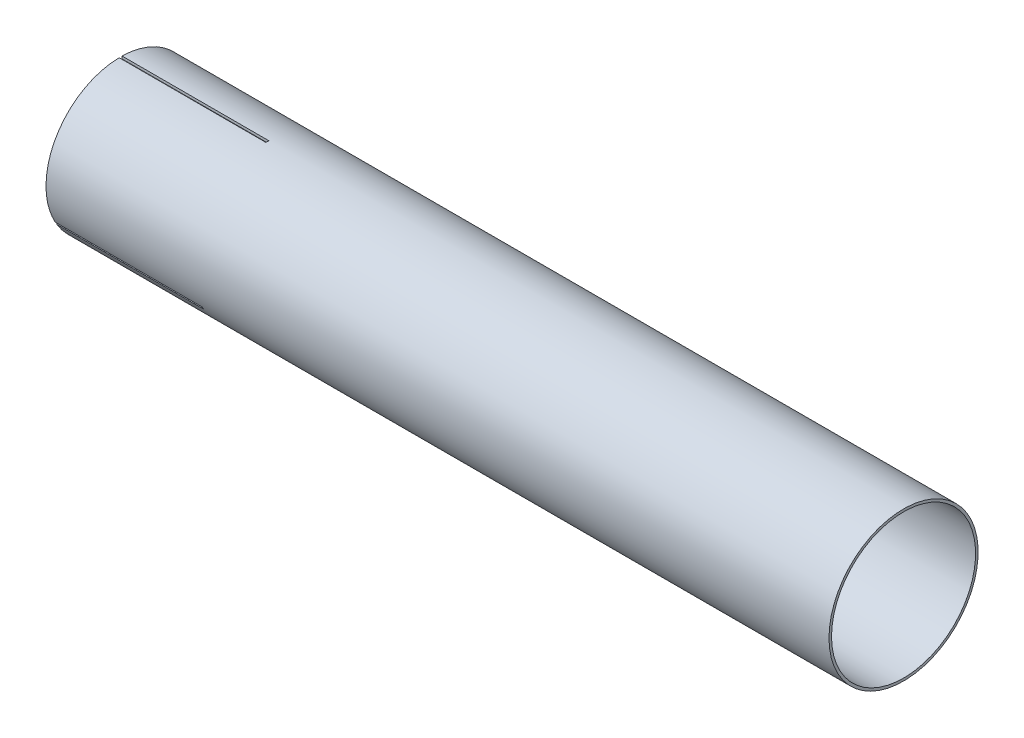
SolidWorks part; units mm, degrees
ref_plane "Plan de face" through (0, 0, 0) normal (0, 0, 1) x (1, 0, 0)
ref_plane "Plan de dessus" through (0, 0, 0) normal (0, 1, 0) x (1, 0, 0)
ref_plane "Plan de droite" through (0, 0, 0) normal (1, 0, 0) x (0, 0, -1)
sketch "Esquisse1" plane through (0, 0, 0) normal (0, 0, 1) x (1, 0, 0)
  line L0 (0, 0) -> (0, 76.2) construction
  line L1 (0, 0) -> (142.5133, 0) construction
  line L2 (0, 76.2) -> (800, 76.2)
  line L3 (0, 76.2) -> (0, -76.2) construction
  line L4 (0, 73.6092) -> (800, 73.6092)
  line L5 (800, 76.2) -> (800, 73.6092)
  line L6 (0, -76.2) -> (800, -76.2) construction
  line L7 (0, 76.2) -> (0, 73.6092)
  dimension "D1" = 152.4
  dimension "D2" = 2.5908
  dimension "D3" = 800
revolve "Révolution1" add sketch "Esquisse1" angle 360 about L1
sketch "Esquisse2" plane through (0, 0, 0) normal (0, 1, 0) x (1, 0, 0)
  line L0 (0, 76.2) -> (0, -76.2) construction
  line L1 (0, -1.5) -> (150, -1.5)
  line L2 (0, -1.5) -> (0, 1.5)
  line L3 (0, 1.5) -> (150, 1.5)
  line L4 (150, -1.5) -> (150, 1.5)
  dimension "D1" = 3
  dimension "D2" = 150
extrude "Enlèv. mat.-Extru.1" cut sketch "Esquisse2" along normal through all
pattern_circular "Répétition circulaire1" count 3 over 240 about axis through (800, 0, 0) along (-1, 0, 0) of "Enlèv. mat.-Extru.1"
